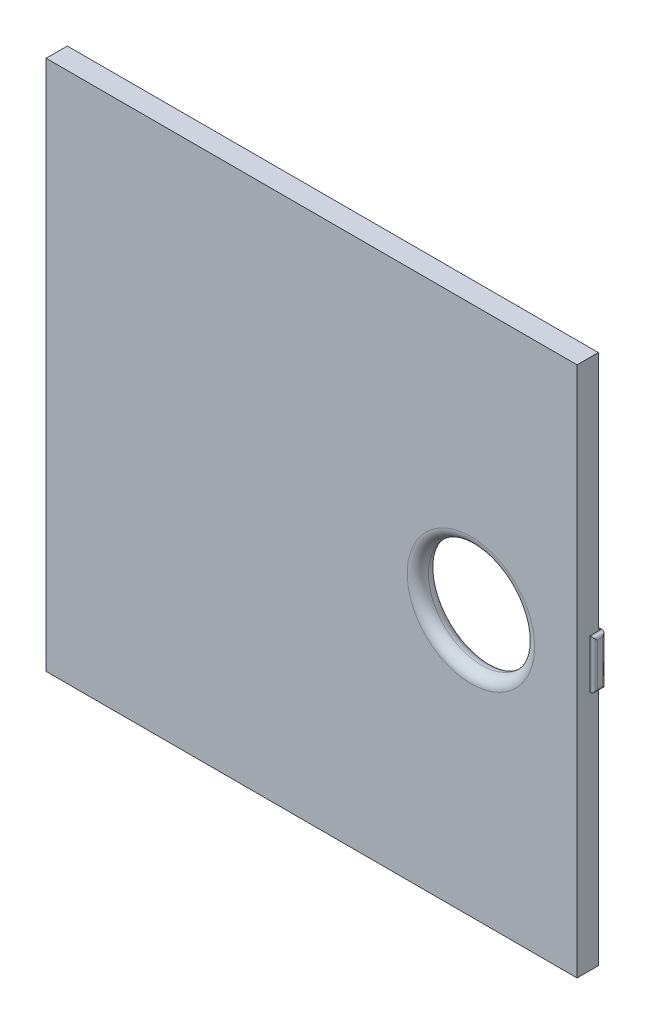
SolidWorks part; units mm, degrees
ref_plane "Front Plane" through (0, 0, 0) normal (0, 0, 1) x (1, 0, 0)
ref_plane "Top Plane" through (0, 0, 0) normal (0, 1, 0) x (1, 0, 0)
ref_plane "Right Plane" through (0, 0, 0) normal (1, 0, 0) x (0, 0, -1)
sketch "Sketch1" plane through (0, 0, 0) normal (0, 0, 1) x (1, 0, 0)
  line L1 (-25, 25) -> (25, 25)
  line L2 (-25, 25) -> (-25, -25)
  line L3 (-25, -25) -> (25, -25)
  line L4 (25, 25) -> (25, -25)
  line L5 (-25, 25) -> (25, -25) construction
  line L6 (-25, -25) -> (25, 25) construction
  point P0 (0, 0)
  dimension "D1" = 50
extrude "Boss-Extrude1" add sketch "Sketch1" along normal blind 2
sketch "Sketch3" plane through (-25, 0, 0) normal (-1, 0, 0) x (0, 0, 1)
  line L0 (1, 21.3) -> (-0.5, 21.3) construction
  line L1 (1, 21.3) -> (-0.5, 21.3)
  line L2 (-0.5, 21.3) -> (-0.5, 18.3) construction
  line L3 (-0.5, 18.3) -> (1, 18.3) construction
  line L4 (1, 18.3) -> (1, 21.3) construction
  line L5 (-0.5, 21.3) -> (-0.5, 18.3)
  line L6 (-0.5, 18.3) -> (1, 18.3)
  line L7 (1, 18.3) -> (1, 21.3)
  line L8 (0, 0) -> (2, 0) construction
  line L9 (2, 25) -> (2, -25) construction
  line L10 (-0.3, 21.1) -> (-0.3, 18.5)
  line L11 (-0.3, 18.5) -> (0.8, 18.5)
  line L12 (0.8, 18.5) -> (0.8, 21.1)
  line L13 (0.8, 21.1) -> (-0.3, 21.1)
  line L14 (-0.3, -21.1) -> (-0.3, -18.5)
  line L15 (-0.3, -18.5) -> (0.8, -18.5)
  line L16 (0.8, -18.5) -> (0.8, -21.1)
  line L17 (0.8, -21.1) -> (-0.3, -21.1)
  dimension "D1" = 0.2
extrude "Boss-Extrude2" add sketch "Sketch3" along normal blind 1.2 and the other way blind 1.2 contours L10 L11 L12 L13 | L14 L15 L16 L17
fillet "Fillet1" radius 1 8 edges at (-24.4, 21.1, 0) (-24.4, 18.5, 0) (-24.4, -21.1, 0) (-24.4, -18.5, 0) (-23.8, -19.8, 0) (-23.8, 19.8, 0) (-25, -19.8, 0.8) (-25, 19.8, 0.8)
sketch "Sketch6" plane through (25, 0, 0) normal (1, 0, 0) x (0, 0, -1)
  line L0 (0.5, -2.5) -> (-1, -2.5) construction
  line L1 (0.5, -2.5) -> (-1, -2.5)
  line L2 (-1, -2.5) -> (-1, 2.5) construction
  line L3 (-1, 2.5) -> (0.5, 2.5) construction
  line L4 (0.5, 2.5) -> (0.5, -2.5) construction
  line L5 (-1, -2.5) -> (-1, 2.5)
  line L6 (-1, 2.5) -> (0.5, 2.5)
  line L7 (0.5, 2.5) -> (0.5, -2.5)
  line L8 (-0.8, 2.3) -> (0.3, 2.3)
  line L9 (0.3, 2.3) -> (0.3, -2.3)
  line L10 (0.3, -2.3) -> (-0.8, -2.3)
  line L11 (-0.8, -2.3) -> (-0.8, 2.3)
  dimension "D1" = 0.2
extrude "Boss-Extrude3" add sketch "Sketch6" along normal blind 0.4 and the other way blind 1.2 contours L9 L10 L11 L8
fillet "Fillet2" radius 0.3 4 edges at (25.4, 0, -0.3) (25.4, -2.3, 0.25) (25.4, 0, 0.8) (25.4, 2.3, 0.25)
fillet "Fillet3" radius 0.3 3 edges at (24.4, -2.3, 0) (24.4, 2.3, 0) (23.8, 0, 0)
sketch "Sketch7" plane through (0, 0, 2) normal (0, 0, 1) x (1, 0, 0)
  line L0 (25, 0) -> (-25, 0) construction
  line L1 (25, -25) -> (25, 25) construction
  line L2 (-25, 25) -> (-25, -25) construction
  circle A0 centre (15, 0) radius 5
  dimension "D1" = 10
  dimension "D2" = 10
extrude "Cut-Extrude1" cut sketch "Sketch7" against normal up to next
fillet "Fillet5" radius 1 2 edges at (20, 0, 0) (20, 0, 2)
